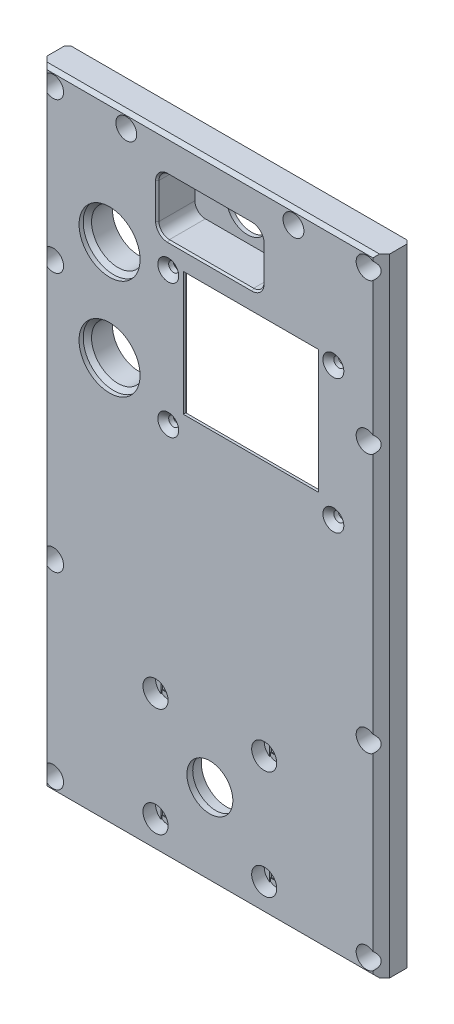
SolidWorks part; units mm, degrees
ref_plane "Front Plane" through (0, 0, 0) normal (0, 0, 1) x (1, 0, 0)
ref_plane "Top Plane" through (0, 0, 0) normal (0, 1, 0) x (1, 0, 0)
ref_plane "Right Plane" through (0, 0, 0) normal (1, 0, 0) x (0, 0, -1)
sketch "Sketch1" plane through (0, 0, 0) normal (0, 0, 1) x (1, 0, 0)
  line L1 (-41, -75) -> (41, -75)
  line L2 (-41, -75) -> (-41, 75)
  line L3 (-41, 75) -> (41, 75)
  line L4 (41, -75) -> (41, 75)
  line L5 (-41, -75) -> (41, 75) construction
  line L6 (-41, 75) -> (41, -75) construction
  line L7 (-34, -68) -> (34, -68)
  line L8 (-34, -68) -> (-34, 68)
  line L9 (-34, 68) -> (34, 68)
  line L10 (34, -68) -> (34, 68)
  line L11 (-34, -68) -> (34, 68) construction
  line L12 (-34, 68) -> (34, -68) construction
  point P0 (0, 0)
  point P6 (0, 0)
  dimension "D1" = 150
  dimension "D2" = 82
  dimension "D3" = 7
  dimension "D4" = 7
extrude "Boss-Extrude1" add sketch "Sketch1" along normal blind 7
sketch "Sketch2" plane through (0, 0, 7) normal (0, 0, 1) x (1, 0, 0)
  line L0 (34, -68) -> (34, 68) construction
  line L1 (-34, -68) -> (34, -68)
  line L2 (-34, -68) -> (-34, -32)
  line L3 (-34, -32) -> (34, -32)
  line L4 (34, -68) -> (34, -32)
  dimension "D1" = 36
extrude "Boss-Extrude2" add sketch "Sketch2" against normal up to surface (7 mm away) up to face at (0, 0, 0)
sketch "Sketch3" plane through (0, 0, 0) normal (0, 0, -1) x (-1, 0, 0)
  line L0 (0, -75) -> (0, -55) construction
  line L1 (41, -75) -> (-41, -75) construction
  circle A0 centre (0, -55) radius 5.5
  dimension "D1" = 11
  dimension "D2" = 20
extrude "Cut-Extrude1" cut sketch "Sketch3" against normal through all
sketch "Sketch4" plane through (0, 0, 0) normal (0, 0, -1) x (-1, 0, 0)
  circle A0 centre (0, -55) radius 6.05
  dimension "D1" = 12.1
extrude "Cut-Extrude2" cut sketch "Sketch4" against normal offset from surface (5.6 mm away) 1.4 up to face at (-5.5, -55, 7)
sketch "Sketch5" plane through (0, 0, 0) normal (0, 0, -1) x (-1, 0, 0)
  circle A0 centre (0, -55) radius 11.1
  dimension "D1" = 22.2
extrude "Cut-Extrude3" cut sketch "Sketch5" against normal offset from surface (3 mm away) 2.6 up to face at (-6.05, -55, 5.6)
sketch "Sketch6" plane through (0, 0, 0) normal (0, 0, -1) x (-1, 0, 0)
  line L1 (-13, -68) -> (13, -68) construction
  line L2 (-13, -68) -> (-13, -42) construction
  line L3 (-13, -42) -> (13, -42) construction
  line L4 (13, -68) -> (13, -42) construction
  line L5 (-13, -68) -> (13, -42) construction
  line L6 (-13, -42) -> (13, -68) construction
  circle A0 centre (-13, -42) radius 1.7
  circle A1 centre (13, -42) radius 1.7
  circle A2 centre (13, -68) radius 1.7
  circle A3 centre (-13, -68) radius 1.7
  point P0 (0, -55)
  dimension "D2" = 3.4
  dimension "D1" = 26
extrude "Cut-Extrude4" cut sketch "Sketch6" against normal through all
sketch "Sketch7" plane through (0, 0, 0) normal (0, 0, -1) x (-1, 0, 0)
  line L1 (-25, -74) -> (25, -74)
  line L2 (-25, -74) -> (-25, -36)
  line L3 (-25, -36) -> (25, -36)
  line L4 (25, -74) -> (25, -36)
  line L5 (-25, -74) -> (25, -36) construction
  line L6 (-25, -36) -> (25, -74) construction
  point P0 (0, -55)
  dimension "D1" = 50
  dimension "D2" = 38
extrude "Cut-Extrude5" cut sketch "Sketch7" against normal blind 1
sketch "Sketch8" plane through (0, 0, 7) normal (0, 0, 1) x (1, 0, 0)
  circle A0 centre (-13, -42) radius 3
  circle A1 centre (13, -42) radius 3
  circle A2 centre (13, -68) radius 3
  circle A3 centre (-13, -68) radius 3
  dimension "D1" = 6
extrude "Cut-Extrude6" cut sketch "Sketch8" against normal blind 3
sketch "Sketch9" plane through (0, 0, 7) normal (0, 0, 1) x (1, 0, 0)
  line L0 (-41, 75) -> (-41, -75) construction
  line L1 (-37.5, -71.5) -> (37.5, -71.5) construction
  line L2 (-37.5, -71.5) -> (-37.5, 71.5) construction
  line L3 (-37.5, 71.5) -> (37.5, 71.5) construction
  line L4 (37.5, -71.5) -> (37.5, 71.5) construction
  line L5 (-37.5, -71.5) -> (37.5, 71.5) construction
  line L6 (-37.5, 71.5) -> (37.5, -71.5) construction
  line L7 (41, 75) -> (-41, 75) construction
  circle A0 centre (-37.5, 71.5) radius 1.45
  circle A1 centre (37.5, 71.5) radius 1.45
  circle A2 centre (37.5, -71.5) radius 1.45
  circle A3 centre (-37.5, -71.5) radius 1.45
  circle A6 centre (-37.5, 35.5) radius 1.45
  circle A7 centre (-37.5, -26.5) radius 1.45
  circle A8 centre (37.5, -26.5) radius 1.45
  circle A9 centre (37.5, 35.5) radius 1.45
  point P0 (0, 0)
  dimension "D3" = 2.9
  dimension "D4" = 45
  dimension "D5" = 36
  dimension "D1" = 3.5
  dimension "D2" = 3.5
extrude "Cut-Extrude7" cut sketch "Sketch9" against normal through all
sketch "Sketch10" plane through (0, 0, 7) normal (0, 0, 1) x (1, 0, 0)
  circle A0 centre (-37.5, 71.5) radius 2.5
  circle A1 centre (37.5, 71.5) radius 2.5
  circle A2 centre (-37.5, 35.5) radius 2.5
  circle A3 centre (-37.5, -26.5) radius 2.5
  circle A4 centre (-37.5, -71.5) radius 2.5
  circle A5 centre (37.5, -71.5) radius 2.5
  circle A6 centre (37.5, 35.5) radius 2.5
  circle A7 centre (37.5, -26.5) radius 2.5
  dimension "D1" = 5
extrude "Cut-Extrude8" cut sketch "Sketch10" against normal blind 5
chamfer "Chamfer1" distance 2 angle 45 2 edges at (-41, 0, 7) (41, 0, 7)
sketch "Sketch11" plane through (0, 0, 7) normal (0, 0, 1) x (1, 0, 0)
  line L0 (34, -32) -> (34, 68) construction
  line L1 (-34, -32) -> (34, -32)
  line L2 (-34, -32) -> (-34, -1.5)
  line L3 (-34, -1.5) -> (34, -1.5)
  line L4 (34, -32) -> (34, -1.5)
  line L5 (-39, -75) -> (39, -75) construction
  dimension "D1" = 73.5
extrude "Boss-Extrude3" add sketch "Sketch11" against normal up to surface (7 mm away) up to face at (38.95, 71.5, 0)
sketch "Sketch12" plane through (0, 0, 2) normal (0, 0, 1) x (1, 0, 0)
  line L2 (-38.95, -73.5365) -> (-38.95, -69.4635)
  line L4 (-36.05, -73.5365) -> (-36.05, -69.4635)
  line L5 (-38.95, -73.5365) -> (-36.05, -69.4635) construction
  line L6 (-38.95, -69.4635) -> (-36.05, -73.5365) construction
  line L8 (-38.95, -28.5365) -> (-38.95, -24.4635)
  line L10 (-36.05, -28.5365) -> (-36.05, -24.4635)
  line L11 (-38.95, -28.5365) -> (-36.05, -24.4635) construction
  line L12 (-38.95, -24.4635) -> (-36.05, -28.5365) construction
  line L14 (-38.95, 33.4635) -> (-38.95, 37.5365)
  line L16 (-36.05, 33.4635) -> (-36.05, 37.5365)
  line L17 (-38.95, 33.4635) -> (-36.05, 37.5365) construction
  line L18 (-38.95, 37.5365) -> (-36.05, 33.4635) construction
  line L20 (-38.95, 69.4635) -> (-38.95, 73.5365)
  line L22 (-36.05, 69.4635) -> (-36.05, 73.5365)
  line L23 (-38.95, 69.4635) -> (-36.05, 73.5365) construction
  line L24 (-38.95, 73.5365) -> (-36.05, 69.4635) construction
  arc A0 (-39, -73.5) -> (-39, -69.5) centre (-37.5, -71.5) ccw construction
  circle A1 centre (-37.5, -26.5) radius 2.5 construction
  circle A2 centre (-37.5, 35.5) radius 2.5 construction
  arc A3 (-39, 69.5) -> (-39, 73.5) centre (-37.5, 71.5) ccw construction
  circle A4 centre (-37.5, 71.5) radius 1.45 construction
  circle A5 centre (-37.5, 71.5) radius 2.5 construction
  arc A6 (-36.05, 73.5365) -> (-38.95, 73.5365) centre (-37.5, 71.5) ccw
  arc A7 (-38.95, 69.4635) -> (-36.05, 69.4635) centre (-37.5, 71.5) ccw
  circle A8 centre (-37.5, 35.5) radius 1.45 construction
  arc A9 (-38.95, 33.4635) -> (-36.05, 33.4635) centre (-37.5, 35.5) ccw
  arc A10 (-36.05, 37.5365) -> (-38.95, 37.5365) centre (-37.5, 35.5) ccw
  circle A11 centre (-37.5, -26.5) radius 1.45 construction
  arc A12 (-38.95, -28.5365) -> (-36.05, -28.5365) centre (-37.5, -26.5) ccw
  arc A13 (-36.05, -24.4635) -> (-38.95, -24.4635) centre (-37.5, -26.5) ccw
  circle A14 centre (-37.5, -71.5) radius 1.45 construction
  arc A16 (-38.95, -73.5365) -> (-36.05, -73.5365) centre (-37.5, -71.5) ccw
  arc A18 (-36.05, -69.4635) -> (-38.95, -69.4635) centre (-37.5, -71.5) ccw
  point P0 (-37.5, -71.5)
  point P9 (-37.5, -26.5)
  point P17 (-37.5, 35.5)
  point P25 (-37.5, 71.5)
extrude "Cut-Extrude9" cut sketch "Sketch12" against normal blind 0.2
sketch "Sketch13" plane through (0, 0, 1.8) normal (0, 0, 1) x (1, 0, 0)
  line L0 (-36.05, -71.5) -> (-36.05, -69.4635) construction
  line L1 (-38.95, -72.95) -> (-36.05, -72.95)
  line L2 (-38.95, -72.95) -> (-38.95, -70.05)
  line L3 (-38.95, -70.05) -> (-36.05, -70.05)
  line L4 (-36.05, -72.95) -> (-36.05, -70.05)
  line L5 (-38.95, -72.95) -> (-36.05, -70.05) construction
  line L6 (-38.95, -70.05) -> (-36.05, -72.95) construction
  line L7 (-36.05, -26.5) -> (-36.05, -24.4635) construction
  line L8 (-38.95, -27.95) -> (-36.05, -27.95)
  line L9 (-38.95, -27.95) -> (-38.95, -25.05)
  line L10 (-38.95, -25.05) -> (-36.05, -25.05)
  line L11 (-36.05, -27.95) -> (-36.05, -25.05)
  line L12 (-38.95, -27.95) -> (-36.05, -25.05) construction
  line L13 (-38.95, -25.05) -> (-36.05, -27.95) construction
  line L14 (-36.05, 33.4635) -> (-36.05, 37.5365) construction
  line L15 (-38.95, 34.05) -> (-36.05, 34.05)
  line L16 (-38.95, 34.05) -> (-38.95, 36.95)
  line L17 (-38.95, 36.95) -> (-36.05, 36.95)
  line L18 (-36.05, 34.05) -> (-36.05, 36.95)
  line L19 (-38.95, 34.05) -> (-36.05, 36.95) construction
  line L20 (-38.95, 36.95) -> (-36.05, 34.05) construction
  line L21 (-36.05, 69.4635) -> (-36.05, 73.5365) construction
  line L22 (-38.95, 70.05) -> (-36.05, 70.05)
  line L23 (-38.95, 70.05) -> (-38.95, 72.95)
  line L24 (-38.95, 72.95) -> (-36.05, 72.95)
  line L25 (-36.05, 70.05) -> (-36.05, 72.95)
  line L26 (-38.95, 70.05) -> (-36.05, 72.95) construction
  line L27 (-38.95, 72.95) -> (-36.05, 70.05) construction
  arc A0 (-36.05, -71.5) -> (-38.95, -71.5) centre (-37.5, -71.5) ccw construction
  arc A1 (-36.05, -26.5) -> (-38.95, -26.5) centre (-37.5, -26.5) ccw construction
  arc A2 (-36.05, 35.5) -> (-38.95, 35.5) centre (-37.5, 35.5) ccw construction
  arc A3 (-36.05, 71.5) -> (-38.95, 71.5) centre (-37.5, 71.5) ccw construction
  point P0 (-37.5, -71.5)
  point P11 (-37.5, -26.5)
  point P22 (-37.5, 35.5)
  point P33 (-37.5, 71.5)
extrude "Cut-Extrude10" cut sketch "Sketch13" against normal blind 0.2
sketch "Sketch14" plane through (0, 0, 4) normal (0, 0, 1) x (1, 0, 0)
  line L2 (-14.7, -44.4718) -> (-14.7, -39.5282)
  line L4 (-11.3, -44.4718) -> (-11.3, -39.5282)
  line L5 (-14.7, -44.4718) -> (-11.3, -39.5282) construction
  line L6 (-14.7, -39.5282) -> (-11.3, -44.4718) construction
  line L8 (-14.7, -70.4718) -> (-14.7, -65.5282)
  line L10 (-11.3, -70.4718) -> (-11.3, -65.5282)
  line L11 (-14.7, -70.4718) -> (-11.3, -65.5282) construction
  line L12 (-14.7, -65.5282) -> (-11.3, -70.4718) construction
  circle A0 centre (-13, -42) radius 3 construction
  circle A1 centre (-13, -68) radius 3 construction
  circle A2 centre (-13, -42) radius 3 construction
  arc A3 (-14.7, -44.4718) -> (-11.3, -44.4718) centre (-13, -42) ccw
  arc A4 (-14.7, -70.4718) -> (-11.3, -70.4718) centre (-13, -68) ccw
  circle A5 centre (-13, -42) radius 1.7 construction
  circle A6 centre (-13, -68) radius 1.7 construction
  arc A7 (-11.3, -39.5282) -> (-14.7, -39.5282) centre (-13, -42) ccw
  arc A8 (-11.3, -65.5282) -> (-14.7, -65.5282) centre (-13, -68) ccw
  point P0 (-13, -42)
  point P8 (-13, -68)
extrude "Cut-Extrude11" cut sketch "Sketch14" against normal blind 0.2
sketch "Sketch15" plane through (0, 0, 3.8) normal (0, 0, 1) x (1, 0, 0)
  line L0 (-11.3, -42) -> (-11.3, -39.5282) construction
  line L1 (-14.7, -43.7) -> (-11.3, -43.7)
  line L2 (-14.7, -43.7) -> (-14.7, -40.3)
  line L3 (-14.7, -40.3) -> (-11.3, -40.3)
  line L4 (-11.3, -43.7) -> (-11.3, -40.3)
  line L5 (-14.7, -43.7) -> (-11.3, -40.3) construction
  line L6 (-14.7, -40.3) -> (-11.3, -43.7) construction
  line L7 (-11.3, -68) -> (-11.3, -65.5282) construction
  line L8 (-14.7, -69.7) -> (-11.3, -69.7)
  line L9 (-14.7, -69.7) -> (-14.7, -66.3)
  line L10 (-14.7, -66.3) -> (-11.3, -66.3)
  line L11 (-11.3, -69.7) -> (-11.3, -66.3)
  line L12 (-14.7, -69.7) -> (-11.3, -66.3) construction
  line L13 (-14.7, -66.3) -> (-11.3, -69.7) construction
  arc A0 (-11.3, -68) -> (-14.7, -68) centre (-13, -68) ccw construction
  arc A1 (-14.7, -42) -> (-11.3, -42) centre (-13, -42) ccw construction
  point P0 (-13, -42)
  point P8 (-13, -68)
extrude "Cut-Extrude12" cut sketch "Sketch15" against normal blind 0.2
mirror "Mirror1" about plane through (0, 0, 0) normal (1, 0, 0) of "Cut-Extrude10", "Cut-Extrude11", "Cut-Extrude12", "Cut-Extrude9"
chamfer "Chamfer3" distance 0.8 angle 45 4 edges at (-41, 0, 0) (41, 0, 0) (0, -75, 7) (0, 75, 7)
sketch "Sketch16" plane through (0, 0, 0) normal (1, 0, 0) x (0, 0, -1)
  line L0 (0, -4) -> (0, -15.4)
  line L1 (0, 75) -> (0, -75) construction
  line L2 (0, -15.4) -> (3.2, -12.2)
  line L3 (3.2, -12.2) -> (3.2, -7.2)
  line L4 (3.2, -7.2) -> (0, -4)
  line L5 (0, -15.4) -> (0, -19.4) construction
  line L6 (0.6, -7.7) -> (2.6, -7.7)
  line L7 (0.6, -7.7) -> (0.6, -11.7)
  line L8 (0.6, -11.7) -> (2.6, -11.7)
  line L9 (2.6, -7.7) -> (2.6, -11.7)
  line L10 (-1.046, -17.4) -> (12.8392, -17.4) construction
  line L11 (2.6, -27.1) -> (2.6, -23.1)
  line L12 (0.6, -23.1) -> (2.6, -23.1)
  line L13 (0.6, -27.1) -> (0.6, -23.1)
  line L14 (0.6, -27.1) -> (2.6, -27.1)
  line L15 (3.2, -27.6) -> (0, -30.8)
  line L16 (3.2, -22.6) -> (3.2, -27.6)
  line L17 (0, -19.4) -> (3.2, -22.6)
  line L18 (0, -30.8) -> (0, -19.4)
  point P10 (2.6, -9.7)
  point P11 (3.2, -9.7)
  point P24 (0, -17.4)
  dimension "D1" = 5
  dimension "D2" = 2
  dimension "D3" = 0.6
  dimension "D4" = 0.6
  dimension "D5" = 45
  dimension "D6" = 4
  dimension "D7" = 4
  dimension "D8" = 4
extrude "Boss-Extrude4" add sketch "Sketch16" along normal mid plane 2
pattern_linear "LPattern1" count 2 spacing 20 along (1, 0, 0) count 2 spacing 20 along (-1, 0, 0) of "Boss-Extrude4"
sketch "Sketch17" plane through (0, 0, 0) normal (0, 0, -1) x (-1, 0, 0)
  line L0 (-20, 71.5) -> (20, 71.5) construction
  line L1 (-40.2, 75) -> (40.2, 75) construction
  circle A0 centre (-37.5, 71.5) radius 1.45 construction
  circle A1 centre (-37.5, 71.5) radius 1.45 construction
  circle A2 centre (-20, 71.5) radius 1.45
  circle A3 centre (20, 71.5) radius 1.45
  point P3 (0, 71.5)
  point P6 (0, 75)
  dimension "D1" = 40
extrude "Cut-Extrude13" cut sketch "Sketch17" against normal through all
sketch "Sketch18" plane through (0, 0, 7) normal (0, 0, 1) x (1, 0, 0)
  circle A0 centre (-20, 71.5) radius 2.5
  circle A1 centre (20, 71.5) radius 2.5
  arc A2 (-39, 69.5) -> (-39, 73.5) centre (-37.5, 71.5) ccw construction
extrude "Cut-Extrude14" cut sketch "Sketch18" against normal up to surface (5 mm away) up to face at (39.475, 71.5, 2)
sketch "Sketch19" plane through (0, 0, 2) normal (0, 0, 1) x (1, 0, 0)
  line L2 (-21.45, 69.4635) -> (-21.45, 73.5365)
  line L4 (-18.55, 69.4635) -> (-18.55, 73.5365)
  line L5 (-21.45, 69.4635) -> (-18.55, 73.5365) construction
  line L6 (-21.45, 73.5365) -> (-18.55, 69.4635) construction
  line L8 (18.55, 69.4635) -> (18.55, 73.5365)
  line L10 (21.45, 69.4635) -> (21.45, 73.5365)
  line L11 (18.55, 69.4635) -> (21.45, 73.5365) construction
  line L12 (18.55, 73.5365) -> (21.45, 69.4635) construction
  circle A0 centre (-20, 71.5) radius 2.5 construction
  circle A1 centre (20, 71.5) radius 2.5 construction
  circle A2 centre (20, 71.5) radius 1.45 construction
  circle A3 centre (-20, 71.5) radius 1.45 construction
  circle A4 centre (-20, 71.5) radius 2.5 construction
  arc A5 (18.55, 69.4635) -> (21.45, 69.4635) centre (20, 71.5) ccw
  arc A6 (-18.55, 73.5365) -> (-21.45, 73.5365) centre (-20, 71.5) ccw
  arc A7 (21.45, 73.5365) -> (18.55, 73.5365) centre (20, 71.5) ccw
  arc A8 (-21.45, 69.4635) -> (-18.55, 69.4635) centre (-20, 71.5) ccw
  point P0 (-20, 71.5)
  point P8 (20, 71.5)
extrude "Cut-Extrude15" cut sketch "Sketch19" against normal blind 0.2
sketch "Sketch20" plane through (0, 0, 1.8) normal (0, 0, 1) x (1, 0, 0)
  line L0 (-18.55, 69.4635) -> (-18.55, 73.5365) construction
  line L1 (-21.45, 70.05) -> (-18.55, 70.05)
  line L2 (-21.45, 70.05) -> (-21.45, 72.95)
  line L3 (-21.45, 72.95) -> (-18.55, 72.95)
  line L4 (-18.55, 70.05) -> (-18.55, 72.95)
  line L5 (-21.45, 70.05) -> (-18.55, 72.95) construction
  line L6 (-21.45, 72.95) -> (-18.55, 70.05) construction
  line L7 (21.45, 71.5) -> (21.45, 73.5365) construction
  line L8 (18.55, 70.05) -> (21.45, 70.05)
  line L9 (18.55, 70.05) -> (18.55, 72.95)
  line L10 (18.55, 72.95) -> (21.45, 72.95)
  line L11 (21.45, 70.05) -> (21.45, 72.95)
  line L12 (18.55, 70.05) -> (21.45, 72.95) construction
  line L13 (18.55, 72.95) -> (21.45, 70.05) construction
  arc A0 (18.55, 71.5) -> (21.45, 71.5) centre (20, 71.5) ccw construction
  point P0 (-20, 71.5)
  point P8 (20, 71.5)
extrude "Cut-Extrude16" cut sketch "Sketch20" against normal blind 0.2
sketch "Skizze4" plane through (0, 0, 0) normal (0, 0, -1) x (-1, 0, 0)
  line L1 (21, -4) -> (-21, -4)
  line L2 (21, -4) -> (21, -30.8)
  line L3 (21, -30.8) -> (-21, -30.8)
  line L4 (-21, -4) -> (-21, -30.8)
extrude "Schnitt-Linear austragen1" cut sketch "Skizze4" along normal up to surface (3.2 mm away) up to face at (-20, -9.7, -3.2)
sketch "Sketch38" plane through (0, 0, 7) normal (0, 0, 1) x (1, 0, 0)
  line L0 (34, -1.5) -> (34, 68) construction
  line L1 (-34, 68) -> (34, 68)
  line L2 (-34, 68) -> (-34, 12)
  line L3 (-34, 12) -> (34, 12)
  line L4 (34, 68) -> (34, 12)
  dimension "D1" = 56
extrude "Boss-Extrude12" add sketch "Sketch38" against normal up to surface (7 mm away) up to face at (18.55, 71.5, 0)
sketch "Sketch41" plane through (0, 0, 7) normal (0, 0, 1) x (1, 0, 0)
  line L1 (-34, 12) -> (34, 12)
  line L2 (-34, 12) -> (-34, -1.5)
  line L3 (-34, -1.5) -> (34, -1.5)
  line L4 (34, 12) -> (34, -1.5)
extrude "Boss-Extrude13" add sketch "Sketch41" against normal up to surface (7 mm away) up to face at (18.55, 71.5, 0)
sketch "Sketch40" plane through (0, 0, 0) normal (0, 0, -1) x (-1, 0, 0)
  line L0 (-6, 66.6873) -> (-6, -2.4873) construction
  line L1 (-23.8, 15.25) -> (11.8, 15.25) construction
  line L2 (-23.8, 15.25) -> (-23.8, 48.95) construction
  line L3 (-23.8, 48.95) -> (11.8, 48.95) construction
  line L4 (11.8, 15.25) -> (11.8, 48.95) construction
  line L5 (-23.8, 15.25) -> (11.8, 48.95) construction
  line L6 (-23.8, 48.95) -> (11.8, 15.25) construction
  line L7 (-21.2, 17.85) -> (9.2, 17.85) construction
  line L8 (-21.2, 17.85) -> (-21.2, 46.35) construction
  line L9 (-21.2, 46.35) -> (9.2, 46.35) construction
  line L10 (9.2, 17.85) -> (9.2, 46.35) construction
  line L11 (-21.2, 17.85) -> (9.2, 46.35) construction
  line L12 (-21.2, 46.35) -> (9.2, 17.85) construction
  line L13 (-24.05, 15) -> (12.05, 15)
  line L14 (-24.05, 15) -> (-24.05, 49.2)
  line L15 (-24.05, 49.2) -> (12.05, 49.2)
  line L16 (12.05, 15) -> (12.05, 49.2)
  line L17 (-24.05, 15) -> (12.05, 49.2) construction
  line L18 (-24.05, 49.2) -> (12.05, 15) construction
  line L19 (-21, 26.4) -> (9, 26.4) construction
  line L20 (-21, 26.4) -> (-21, 41.6) construction
  line L21 (-21, 41.6) -> (9, 41.6) construction
  line L22 (9, 26.4) -> (9, 41.6) construction
  line L23 (-21, 26.4) -> (9, 41.6) construction
  line L24 (-21, 41.6) -> (9, 26.4) construction
  line L25 (-6, 34) -> (24, 34) construction
  line L26 (24, 22) -> (24, 46) construction
  circle A0 centre (-21.2, 46.35) radius 1.5 construction
  circle A1 centre (9.2, 46.35) radius 1.5 construction
  circle A2 centre (9.2, 17.85) radius 1.5 construction
  circle A3 centre (-21.2, 17.85) radius 1.5 construction
  circle A4 centre (24, 46) radius 6.3
  circle A5 centre (24, 22) radius 6.3
  circle A6 centre (24, 22) radius 7
  circle A7 centre (24, 46) radius 7
  point P2 (-6, 32.1)
  point P7 (-6, 32.1)
  point P16 (-6, 32.1)
  point P21 (-6, 34)
  point P32 (24, 34)
  dimension "D5" = 3
  dimension "D12" = 6
  dimension "D13" = 12.6
  dimension "D14" = 14
  dimension "D1" = 35.6
  dimension "D2" = 33.7
  dimension "D3" = 30.4
  dimension "D4" = 28.5
  dimension "D6" = 0.25
  dimension "D7" = 0.25
  dimension "D8" = 15.2
  dimension "D9" = 30
  dimension "D10" = 7.35
  dimension "D11" = 15
  dimension "D15" = 24
  dimension "D16" = 30
sketch "Sketch42" plane through (0, 0, 0) normal (0, 0, -1) x (-1, 0, 0)
  line L0 (-24.05, 15) -> (12.05, 15) construction
  line L1 (12.05, 15) -> (12.05, 49.2) construction
  line L2 (-24.05, 49.2) -> (12.05, 49.2) construction
  line L3 (-24.05, 15) -> (-24.05, 49.2) construction
  line L4 (-24.05, 15) -> (12.05, 15)
  line L5 (12.05, 15) -> (12.05, 49.2)
  line L6 (-24.05, 49.2) -> (12.05, 49.2)
  line L7 (-24.05, 15) -> (-24.05, 49.2)
sketch "Sketch44" plane through (0, 0, 0) normal (0, 0, -1) x (-1, 0, 0)
  circle A0 centre (24, 22) radius 6.3 construction
  circle A1 centre (24, 46) radius 6.3 construction
  circle A2 centre (24, 22) radius 6.3
  circle A3 centre (24, 46) radius 6.3
extrude "Cut-Extrude19" cut sketch "Sketch44" against normal through all
sketch "Sketch47" plane through (0, 0, 0) normal (0, 0, -1) x (-1, 0, 0)
  line L1 (-28.79, 50.463) -> (15.71, 50.463)
  line L2 (-28.79, 50.463) -> (-28.79, 13.463)
  line L3 (-28.79, 13.463) -> (15.71, 13.463)
  line L4 (15.71, 50.463) -> (15.71, 13.463)
  dimension "D1" = 44.5
  dimension "D2" = 37
sketch "Sketch48" plane through (0, 0, 0) normal (0, 0, -1) x (-1, 0, 0)
  line L1 (-17.5, 51.3083) -> (17.5, 51.3083)
  line L2 (-17.5, 51.3083) -> (-17.5, 71.3083)
  line L3 (-17.5, 71.3083) -> (17.5, 71.3083)
  line L4 (17.5, 51.3083) -> (17.5, 71.3083)
  line L5 (-17.5, 51.3083) -> (17.5, 71.3083) construction
  line L6 (-17.5, 71.3083) -> (17.5, 51.3083) construction
  point P0 (0, 61.3083)
  dimension "D1" = 35
  dimension "D2" = 20
sketch "Sketch49" plane through (0, 0, 7) normal (0, 0, 1) x (1, 0, 0)
  line L0 (-39.8, 75) -> (39.8, 75) construction
  line L1 (-12.575, 53.25) -> (12.575, 53.25)
  line L2 (-12.575, 53.25) -> (-12.575, 66.75)
  line L3 (-12.575, 66.75) -> (12.575, 66.75)
  line L4 (12.575, 53.25) -> (12.575, 66.75)
  line L5 (-12.575, 53.25) -> (12.575, 66.75) construction
  line L6 (-12.575, 66.75) -> (12.575, 53.25) construction
  point P0 (0, 60)
  dimension "D1" = 25.15
  dimension "D2" = 13.5
  dimension "D3" = 15
extrude "Cut-Extrude20" cut sketch "Sketch49" against normal through all
sketch "Sketch50" plane through (0, 0, 0) normal (0, 0, -1) x (-1, 0, 0)
  line L0 (12.575, 66.75) -> (12.575, 53.25) construction
  line L1 (12.575, 53.25) -> (-12.575, 53.25) construction
  line L2 (-12.575, 53.25) -> (-12.575, 66.75) construction
  line L3 (-12.575, 66.75) -> (12.575, 66.75) construction
  line L4 (12.575, 66.75) -> (12.575, 53.25)
  line L5 (12.575, 53.25) -> (-12.575, 53.25)
  line L6 (-12.575, 53.25) -> (-12.575, 66.75)
  line L7 (-12.575, 66.75) -> (12.575, 66.75)
  line L8 (12.575, 66.75) -> (-12.575, 53.25) construction
  line L10 (-14.575, 51.25) -> (14.575, 51.25)
  line L11 (-14.575, 51.25) -> (-14.575, 68.75)
  line L12 (-14.575, 68.75) -> (14.575, 68.75)
  line L13 (14.575, 51.25) -> (14.575, 68.75)
  line L14 (-14.575, 51.25) -> (14.575, 68.75) construction
  line L15 (-14.575, 68.75) -> (14.575, 51.25) construction
  point P2 (0, 60)
  dimension "D1" = 2
  dimension "D2" = 2
extrude "Boss-Extrude16" add sketch "Sketch50" along normal offset from surface (2 mm away) 9 up to face at (0, 60, 7)
sketch "Sketch51" plane through (0, 0, -2) normal (0, 0, -1) x (-1, 0, 0)
  line L4 (-14.575, 51.25) -> (14.575, 51.25)
  line L5 (14.575, 51.25) -> (14.575, 68.75)
  line L6 (14.575, 68.75) -> (-14.575, 68.75)
  line L7 (-14.575, 68.75) -> (-14.575, 51.25)
  line L8 (-14.575, 51.25) -> (14.575, 51.25)
  line L9 (14.575, 51.25) -> (14.575, 68.75)
  line L10 (14.575, 68.75) -> (-14.575, 68.75)
  line L11 (-14.575, 68.75) -> (-14.575, 51.25)
  dimension "D1" = 0
extrude "Boss-Extrude17" add sketch "Sketch51" along normal blind 1
sketch "Sketch52" plane through (0, 0, -3) normal (0, 0, -1) x (-1, 0, 0)
  line L0 (14.575, 68.75) -> (-14.575, 51.25) construction
  circle A0 centre (0, 60) radius 5
  dimension "D1" = 10
extrude "Cut-Extrude21" cut sketch "Sketch52" against normal through all both and the other way through all
sketch "Sketch53" plane through (12.575, 0, 0) normal (-1, 0, 0) x (0, 0, 1)
  line L0 (-2, 66.75) -> (-2, 53.25) construction
  line L1 (-2, 62.5) -> (6.4, 62.5)
  line L2 (-2, 62.5) -> (-2, 57.5)
  line L3 (-2, 57.5) -> (6.4, 57.5)
  line L4 (6.4, 62.5) -> (6.4, 57.5)
  line L5 (7, 53.25) -> (7, 66.75) construction
  point P8 (6.4, 60)
  point P9 (7, 60)
  dimension "D1" = 0.6
  dimension "D2" = 5
extrude "Cut-Extrude22" cut sketch "Sketch53" against normal blind 6
sketch "Sketch54" plane through (0, 0, 7) normal (0, 0, 1) x (1, 0, 0)
  circle A0 centre (-24, 46) radius 7.3
  circle A1 centre (-24, 22) radius 7.3
  dimension "D1" = 14.6
extrude "Cut-Extrude23" cut sketch "Sketch54" against normal blind 1
chamfer "Chamfer4" distance 1 angle 45 2 edges at (-17.7, 22, 6) (-17.7, 46, 6)
fillet "Fillet1" radius 2.5 4 edges at (12.575, 53.25, 2.5) (-12.575, 53.25, 2.5) (12.575, 66.75, 2.5) (-12.575, 66.75, 2.5)
chamfer "Chamfer5" distance 0.4 angle 45 8 edges at (0, 53.25, 7) (11.8428, 53.9822, 7) (-11.8428, 53.9822, 7) (12.575, 60, 7) (-12.575, 60, 7) (11.8428, 66.0178, 7) (-11.8428, 66.0178, 7) (0, 66.75, 7)
sketch "Sketch55" plane through (0, 0, 0) normal (0, 0, -1) x (-1, 0, 0)
  line L0 (24, 46) -> (24, 22) construction
  line L1 (-32.05, 12.725) -> (12.45, 12.725)
  line L2 (-32.05, 12.725) -> (-32.05, 49.725)
  line L3 (-32.05, 49.725) -> (12.45, 49.725)
  line L4 (12.45, 12.725) -> (12.45, 49.725)
  line L5 (-32.05, 12.725) -> (12.45, 49.725) construction
  line L6 (-32.05, 49.725) -> (12.45, 12.725) construction
  line L7 (-29.55, 47.225) -> (9.95, 47.225) construction
  line L8 (-29.55, 47.225) -> (-29.55, 15.225) construction
  line L9 (-29.55, 15.225) -> (9.95, 15.225) construction
  line L10 (9.95, 47.225) -> (9.95, 15.225) construction
  line L11 (-26.75, 49.525) -> (7.15, 49.525)
  line L12 (-26.75, 49.525) -> (-26.75, 18.325)
  line L13 (-26.75, 18.325) -> (7.15, 18.325)
  line L14 (7.15, 49.525) -> (7.15, 18.325)
  line L15 (-23.225, 47.425) -> (3.625, 47.425)
  line L16 (-23.225, 47.425) -> (-23.225, 20.575)
  line L17 (-23.225, 20.575) -> (3.625, 20.575)
  line L18 (3.625, 47.425) -> (3.625, 20.575)
  circle A0 centre (-29.55, 47.225) radius 1
  circle A1 centre (-29.55, 15.225) radius 1
  circle A2 centre (9.95, 15.225) radius 1
  circle A3 centre (9.95, 47.225) radius 1
  point P0 (-9.8, 31.225)
  point P9 (-9.8, 47.225)
  point P18 (-9.8, 49.525)
  point P19 (-9.8, 15.225)
  point P24 (-9.8, 47.425)
  point P29 (24, 34)
  point P30 (3.625, 34)
  dimension "D5" = 2
  dimension "D1" = 44.5
  dimension "D2" = 37
  dimension "D3" = 39.5
  dimension "D4" = 32
  dimension "D6" = 2.5
  dimension "D7" = 33.9
  dimension "D8" = 31.2
  dimension "D9" = 0.2
  dimension "D10" = 26.85
  dimension "D11" = 2.1
  dimension "D12" = 33.8
sketch "Sketch56" plane through (0, 0, 0) normal (0, 0, -1) x (-1, 0, 0)
  line L17 (-32.65, 12.125) -> (13.05, 12.125)
  line L18 (-32.65, 50.325) -> (-32.65, 12.125)
  line L19 (13.05, 50.325) -> (-32.65, 50.325)
  line L20 (13.05, 12.125) -> (13.05, 50.325)
  line L21 (-32.65, 12.125) -> (13.05, 12.125)
  line L22 (-32.65, 50.325) -> (-32.65, 12.125)
  line L23 (13.05, 50.325) -> (-32.65, 50.325)
  line L24 (13.05, 12.125) -> (13.05, 50.325)
  dimension "D1" = 0.6
extrude "Cut-Extrude24" cut sketch "Sketch56" against normal offset from surface (6.4 mm away) 0.6 up to face at (0, 60, 7)
sketch "Sketch57" plane through (0, 0, 6.4) normal (0, 0, -1) x (-1, 0, 0)
  line L17 (-25.95, 19.125) -> (6.35, 19.125)
  line L18 (6.35, 19.125) -> (6.35, 48.725)
  line L19 (6.35, 48.725) -> (-25.95, 48.725)
  line L20 (-25.95, 48.725) -> (-25.95, 19.125)
  line L21 (-25.95, 19.125) -> (6.35, 19.125)
  line L22 (6.35, 19.125) -> (6.35, 48.725)
  line L23 (6.35, 48.725) -> (-25.95, 48.725)
  line L24 (-25.95, 48.725) -> (-25.95, 19.125)
  dimension "D1" = 0.8
extrude "Cut-Extrude25" cut sketch "Sketch57" against normal through all
sketch "Sketch58" plane through (0, 0, 6.4) normal (0, 0, -1) x (-1, 0, 0)
  line L4 (-32.65, 50.325) -> (13.05, 50.325) construction
  line L5 (-27.55, 50.325) -> (-32.65, 50.325)
  line L6 (-27.55, 50.325) -> (-27.55, 12.125)
  line L7 (-27.55, 12.125) -> (-32.65, 12.125)
  line L8 (-32.65, 50.325) -> (-32.65, 12.125)
  line L9 (-26.75, 49.525) -> (-26.75, 18.325) construction
  line L10 (-9.8, 50.325) -> (-9.8, 12.125) construction
  line L11 (13.05, 50.325) -> (-32.65, 50.325) construction
  line L12 (-32.65, 12.125) -> (13.05, 12.125) construction
  line L13 (13.05, 50.325) -> (13.05, 12.125)
  line L14 (7.95, 12.125) -> (13.05, 12.125)
  line L15 (7.95, 50.325) -> (7.95, 12.125)
  line L16 (7.95, 50.325) -> (13.05, 50.325)
  dimension "D1" = 0.8
extrude "Boss-Extrude18" add sketch "Sketch58" along normal blind 1.8
sketch "Sketch59" plane through (0, 0, 4.6) normal (0, 0, -1) x (-1, 0, 0)
  circle A0 centre (-29.55, 47.225) radius 1.2
  circle A1 centre (9.95, 47.225) radius 1.2
  circle A2 centre (9.95, 15.225) radius 1.2
  circle A3 centre (-29.55, 15.225) radius 1.2
  dimension "D1" = 2.4
extrude "Cut-Extrude26" cut sketch "Sketch59" against normal through all
chamfer "Chamfer6" distance 1.3 angle 45 4 edges at (-11.15, 15.225, 7) (28.35, 15.225, 7) (28.35, 47.225, 7) (-11.15, 47.225, 7)
